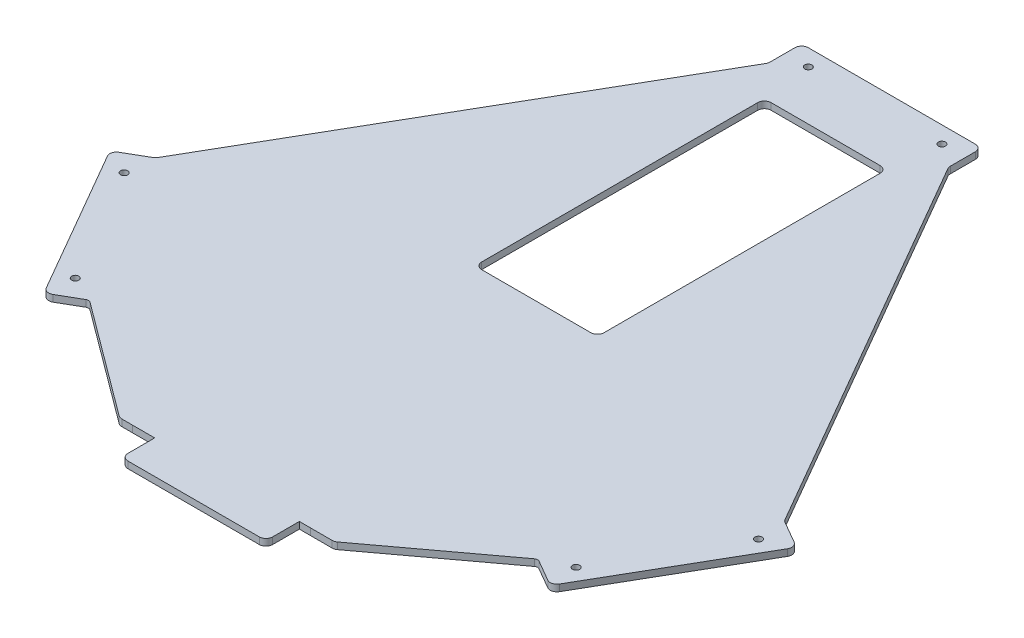
SolidWorks part; units mm, degrees
ref_plane "正面" through (0, 0, 0) normal (0, 0, 1) x (1, 0, 0)
ref_plane "平面" through (0, 0, 0) normal (0, 1, 0) x (1, 0, 0)
ref_plane "右側面" through (0, 0, 0) normal (1, 0, 0) x (0, 0, -1)
sketch "ｽｹｯﾁ1" plane through (0, 0, 0) normal (0, 1, 0) x (1, 0, 0)
  line L0 (341.7223, -98.5666) -> (163.7541, 4.1834) construction
  line L1 (85.5, 139.7235) -> (163.7541, 4.1834) construction
  line L2 (85.5, 345.2235) -> (85.5, 139.7235) construction
  line L3 (-275.2349, -158.9069) -> (275.2349, -158.9069)
  line L4 (275.2349, -158.9069) -> (0, 317.8138)
  line L5 (0, 317.8138) -> (-275.2349, -158.9069)
  line L6 (-275.2349, -158.9069) -> (275.2349, -158.9069)
  line L7 (275.2349, -158.9069) -> (0, 317.8138)
  line L8 (0, 317.8138) -> (-275.2349, -158.9069)
  line L9 (0, 450) -> (-389.7114, -225)
  line L10 (-389.7114, -225) -> (389.7114, -225)
  line L11 (389.7114, -225) -> (0, 450)
  line L12 (0, 450) -> (-389.7114, -225)
  line L13 (-389.7114, -225) -> (389.7114, -225)
  line L14 (389.7114, -225) -> (0, 450)
  line L15 (-70.5, 139.7235) -> (70.5, 139.7235) construction
  line L16 (-85.7541, -130.9165) -> (-156.2541, -8.807) construction
  line L17 (156.2541, -8.807) -> (85.7541, -130.9165) construction
  line L18 (0, 0) -> (259.8076, -150) construction
  line L19 (0, 0) -> (-259.8076, -150) construction
  line L20 (0, 0) -> (0, 300) construction
  line L21 (-341.7223, -98.5666) -> (-163.7541, 4.1834) construction
  line L22 (-163.7541, 4.1834) -> (-85.5, 139.7235) construction
  line L23 (-85.5, 345.2235) -> (-85.5, 139.7235) construction
  line L24 (256.2223, -246.6569) -> (78.2541, -143.9069) construction
  line L25 (78.2541, -143.9069) -> (-78.2541, -143.9069) construction
  line L26 (-256.2223, -246.6569) -> (-78.2541, -143.9069) construction
  line L27 (341.7223, -98.5666) -> (163.7541, 4.1834)
  line L28 (85.5, 139.7235) -> (163.7541, 4.1834)
  line L29 (85.5, 345.2235) -> (85.5, 139.7235)
  line L30 (-70.5, 139.7235) -> (70.5, 139.7235)
  line L31 (-85.7541, -130.9165) -> (-156.2541, -8.807)
  line L32 (156.2541, -8.807) -> (85.7541, -130.9165)
  line L33 (0, 0) -> (259.8076, -150)
  line L34 (0, 0) -> (-259.8076, -150)
  line L35 (0, 0) -> (0, 300)
  line L36 (-341.7223, -98.5666) -> (-163.7541, 4.1834)
  line L37 (-163.7541, 4.1834) -> (-85.5, 139.7235)
  line L38 (-85.5, 345.2235) -> (-85.5, 139.7235)
  line L39 (256.2223, -246.6569) -> (78.2541, -143.9069)
  line L40 (78.2541, -143.9069) -> (-78.2541, -143.9069)
  line L41 (-256.2223, -246.6569) -> (-78.2541, -143.9069)
  line L42 (-40.5, 140.8727) -> (-40.5, 153.6419) construction
  line L43 (-41.4674, 155.2072) -> (-70.1305, 169.5387) construction
  line L44 (-70.9131, 169.7235) -> (-84.4896, 169.7235) construction
  line L45 (-86.0052, 168.8485) -> (-112.6154, 122.7583) construction
  line L46 (-111.9748, 120.3677) -> (-101.2625, 114.1829) construction
  line L47 (-99.6921, 114.0926) -> (-41.5546, 139.2668) construction
  line L48 (70.1305, 169.5387) -> (41.4674, 155.2072) construction
  line L49 (40.5, 153.6419) -> (40.5, 140.8727) construction
  line L50 (41.5546, 139.2668) -> (99.6921, 114.0926) construction
  line L51 (101.2625, 114.1829) -> (111.9748, 120.3677) construction
  line L52 (112.6154, 122.7583) -> (86.0052, 168.8485) construction
  line L53 (84.4896, 169.7235) -> (70.9131, 169.7235) construction
  line L54 (142.2494, -35.3623) -> (153.3078, -41.7469) construction
  line L55 (155.147, -41.6918) -> (181.8901, -24.0346) construction
  line L56 (182.4414, -23.4492) -> (189.2297, -11.6916) construction
  line L57 (189.2297, -9.9416) -> (162.6195, 36.1486) construction
  line L58 (160.2289, 36.7892) -> (149.5165, 30.6044) construction
  line L59 (148.6531, 29.2896) -> (141.3859, -33.6461) construction
  line L60 (111.7596, -145.5042) -> (113.6797, -113.5154) construction
  line L61 (112.8078, -111.895) -> (101.7494, -105.5104) construction
  line L62 (99.8313, -105.6208) -> (48.961, -143.3822) construction
  line L63 (48.2541, -144.7873) -> (48.2541, -157.1569) construction
  line L64 (50.0041, -158.9069) -> (103.2245, -158.9069) construction
  line L65 (104.74, -158.0319) -> (111.5283, -146.2743) construction
  line L66 (-101.7494, -105.5104) -> (-112.8078, -111.895) construction
  line L67 (-113.6797, -113.5154) -> (-111.7596, -145.5042) construction
  line L68 (-111.5283, -146.2743) -> (-104.74, -158.0319) construction
  line L69 (-103.2245, -158.9069) -> (-50.0041, -158.9069) construction
  line L70 (-48.2541, -157.1569) -> (-48.2541, -144.7873) construction
  line L71 (-48.961, -143.3822) -> (-99.8313, -105.6208) construction
  line L72 (-181.8901, -24.0346) -> (-155.147, -41.6918) construction
  line L73 (-153.3078, -41.7469) -> (-142.2494, -35.3623) construction
  line L74 (-141.3859, -33.6461) -> (-148.6531, 29.2896) construction
  line L75 (-149.5165, 30.6044) -> (-160.2289, 36.7892) construction
  line L76 (-162.6195, 36.1486) -> (-189.2297, -9.9416) construction
  line L77 (-189.2297, -11.6916) -> (-182.4414, -23.4492) construction
  line L78 (-40.5, 140.8727) -> (-40.5, 153.6419)
  line L79 (-41.4674, 155.2072) -> (-70.1305, 169.5387)
  line L80 (-70.9131, 169.7235) -> (-84.4896, 169.7235)
  line L81 (-86.0052, 168.8485) -> (-112.6154, 122.7583)
  line L82 (-111.9748, 120.3677) -> (-101.2625, 114.1829)
  line L83 (-99.6921, 114.0926) -> (-41.5546, 139.2668)
  line L84 (70.1305, 169.5387) -> (41.4674, 155.2072)
  line L85 (40.5, 153.6419) -> (40.5, 140.8727)
  line L86 (41.5546, 139.2668) -> (99.6921, 114.0926)
  line L87 (101.2625, 114.1829) -> (111.9748, 120.3677)
  line L88 (112.6154, 122.7583) -> (86.0052, 168.8485)
  line L89 (84.4896, 169.7235) -> (70.9131, 169.7235)
  line L90 (142.2494, -35.3623) -> (153.3078, -41.7469)
  line L91 (155.147, -41.6918) -> (181.8901, -24.0346)
  line L92 (182.4414, -23.4492) -> (189.2297, -11.6916)
  line L93 (189.2297, -9.9416) -> (162.6195, 36.1486)
  line L94 (160.2289, 36.7892) -> (149.5165, 30.6044)
  line L95 (148.6531, 29.2896) -> (141.3859, -33.6461)
  line L96 (111.7596, -145.5042) -> (113.6797, -113.5154)
  line L97 (112.8078, -111.895) -> (101.7494, -105.5104)
  line L98 (99.8313, -105.6208) -> (48.961, -143.3822)
  line L99 (48.2541, -144.7873) -> (48.2541, -157.1569)
  line L100 (50.0041, -158.9069) -> (103.2245, -158.9069)
  line L101 (104.74, -158.0319) -> (111.5283, -146.2743)
  line L102 (-101.7494, -105.5104) -> (-112.8078, -111.895)
  line L103 (-113.6797, -113.5154) -> (-111.7596, -145.5042)
  line L104 (-111.5283, -146.2743) -> (-104.74, -158.0319)
  line L105 (-103.2245, -158.9069) -> (-50.0041, -158.9069)
  line L106 (-48.2541, -157.1569) -> (-48.2541, -144.7873)
  line L107 (-48.961, -143.3822) -> (-99.8313, -105.6208)
  line L108 (-181.8901, -24.0346) -> (-155.147, -41.6918)
  line L109 (-153.3078, -41.7469) -> (-142.2494, -35.3623)
  line L110 (-141.3859, -33.6461) -> (-148.6531, 29.2896)
  line L111 (-149.5165, 30.6044) -> (-160.2289, 36.7892)
  line L112 (-162.6195, 36.1486) -> (-189.2297, -9.9416)
  line L113 (-189.2297, -11.6916) -> (-182.4414, -23.4492)
  arc A0 (-40.5, 153.6419) -> (-41.4674, 155.2072) centre (-42.25, 153.6419) ccw construction
  circle A1 centre (0, 0) radius 300
  circle A2 centre (0, 0) radius 300
  arc A3 (-70.1305, 169.5387) -> (-70.9131, 169.7235) centre (-70.9131, 167.9735) ccw construction
  arc A4 (-84.4896, 169.7235) -> (-86.0052, 168.8485) centre (-84.4896, 167.9735) ccw construction
  arc A5 (-112.6154, 122.7583) -> (-111.9748, 120.3677) centre (-111.0998, 121.8833) ccw construction
  arc A6 (-101.2625, 114.1829) -> (-99.6921, 114.0926) centre (-100.3875, 115.6985) ccw construction
  arc A7 (-41.5546, 139.2668) -> (-40.5, 140.8727) centre (-42.25, 140.8727) ccw construction
  arc A8 (41.4674, 155.2072) -> (40.5, 153.6419) centre (42.25, 153.6419) ccw construction
  arc A9 (40.5, 140.8727) -> (41.5546, 139.2668) centre (42.25, 140.8727) ccw construction
  arc A10 (99.6921, 114.0926) -> (101.2625, 114.1829) centre (100.3875, 115.6985) ccw construction
  arc A11 (111.9748, 120.3677) -> (112.6154, 122.7583) centre (111.0998, 121.8833) ccw construction
  arc A12 (86.0052, 168.8485) -> (84.4896, 169.7235) centre (84.4896, 167.9735) ccw construction
  arc A13 (70.9131, 169.7235) -> (70.1305, 169.5387) centre (70.9131, 167.9735) ccw construction
  arc A14 (153.3078, -41.7469) -> (155.147, -41.6918) centre (154.1828, -40.2314) ccw construction
  arc A15 (181.8901, -24.0346) -> (182.4414, -23.4492) centre (180.9259, -22.5742) ccw construction
  arc A16 (189.2297, -11.6916) -> (189.2297, -9.9416) centre (187.7141, -10.8166) ccw construction
  arc A17 (162.6195, 36.1486) -> (160.2289, 36.7892) centre (161.1039, 35.2736) ccw construction
  arc A18 (149.5165, 30.6044) -> (148.6531, 29.2896) centre (150.3915, 29.0889) ccw construction
  arc A19 (141.3859, -33.6461) -> (142.2494, -35.3623) centre (143.1244, -33.8468) ccw construction
  arc A20 (113.6797, -113.5154) -> (112.8078, -111.895) centre (111.9328, -113.4105) ccw construction
  arc A21 (101.7494, -105.5104) -> (99.8313, -105.6208) centre (100.8744, -107.0259) ccw construction
  arc A22 (48.961, -143.3822) -> (48.2541, -144.7873) centre (50.0041, -144.7873) ccw construction
  arc A23 (48.2541, -157.1569) -> (50.0041, -158.9069) centre (50.0041, -157.1569) ccw construction
  arc A24 (103.2245, -158.9069) -> (104.74, -158.0319) centre (103.2245, -157.1569) ccw construction
  arc A25 (111.5283, -146.2743) -> (111.7596, -145.5042) centre (110.0127, -145.3993) ccw construction
  arc A26 (-112.8078, -111.895) -> (-113.6797, -113.5154) centre (-111.9328, -113.4105) ccw construction
  arc A27 (-111.7596, -145.5042) -> (-111.5283, -146.2743) centre (-110.0127, -145.3993) ccw construction
  arc A28 (-104.74, -158.0319) -> (-103.2245, -158.9069) centre (-103.2245, -157.1569) ccw construction
  arc A29 (-50.0041, -158.9069) -> (-48.2541, -157.1569) centre (-50.0041, -157.1569) ccw construction
  arc A30 (-48.2541, -144.7873) -> (-48.961, -143.3822) centre (-50.0041, -144.7873) ccw construction
  arc A31 (-99.8313, -105.6208) -> (-101.7494, -105.5104) centre (-100.8744, -107.0259) ccw construction
  arc A32 (-155.147, -41.6918) -> (-153.3078, -41.7469) centre (-154.1828, -40.2314) ccw construction
  arc A33 (-142.2494, -35.3623) -> (-141.3859, -33.6461) centre (-143.1244, -33.8468) ccw construction
  arc A34 (-148.6531, 29.2896) -> (-149.5165, 30.6044) centre (-150.3915, 29.0889) ccw construction
  arc A35 (-160.2289, 36.7892) -> (-162.6195, 36.1486) centre (-161.1039, 35.2736) ccw construction
  arc A36 (-189.2297, -9.9416) -> (-189.2297, -11.6916) centre (-187.7141, -10.8166) ccw construction
  arc A37 (-182.4414, -23.4492) -> (-181.8901, -24.0346) centre (-180.9259, -22.5742) ccw construction
  arc A38 (-40.5, 153.6419) -> (-41.4674, 155.2072) centre (-42.25, 153.6419) ccw
  arc A39 (-70.1305, 169.5387) -> (-70.9131, 169.7235) centre (-70.9131, 167.9735) ccw
  arc A40 (-84.4896, 169.7235) -> (-86.0052, 168.8485) centre (-84.4896, 167.9735) ccw
  arc A41 (-112.6154, 122.7583) -> (-111.9748, 120.3677) centre (-111.0998, 121.8833) ccw
  arc A42 (-101.2625, 114.1829) -> (-99.6921, 114.0926) centre (-100.3875, 115.6985) ccw
  arc A43 (-41.5546, 139.2668) -> (-40.5, 140.8727) centre (-42.25, 140.8727) ccw
  arc A44 (41.4674, 155.2072) -> (40.5, 153.6419) centre (42.25, 153.6419) ccw
  arc A45 (40.5, 140.8727) -> (41.5546, 139.2668) centre (42.25, 140.8727) ccw
  arc A46 (99.6921, 114.0926) -> (101.2625, 114.1829) centre (100.3875, 115.6985) ccw
  arc A47 (111.9748, 120.3677) -> (112.6154, 122.7583) centre (111.0998, 121.8833) ccw
  arc A48 (86.0052, 168.8485) -> (84.4896, 169.7235) centre (84.4896, 167.9735) ccw
  arc A49 (70.9131, 169.7235) -> (70.1305, 169.5387) centre (70.9131, 167.9735) ccw
  arc A50 (153.3078, -41.7469) -> (155.147, -41.6918) centre (154.1828, -40.2314) ccw
  arc A51 (181.8901, -24.0346) -> (182.4414, -23.4492) centre (180.9259, -22.5742) ccw
  arc A52 (189.2297, -11.6916) -> (189.2297, -9.9416) centre (187.7141, -10.8166) ccw
  arc A53 (162.6195, 36.1486) -> (160.2289, 36.7892) centre (161.1039, 35.2736) ccw
  arc A54 (149.5165, 30.6044) -> (148.6531, 29.2896) centre (150.3915, 29.0889) ccw
  arc A55 (141.3859, -33.6461) -> (142.2494, -35.3623) centre (143.1244, -33.8468) ccw
  arc A56 (113.6797, -113.5154) -> (112.8078, -111.895) centre (111.9328, -113.4105) ccw
  arc A57 (101.7494, -105.5104) -> (99.8313, -105.6208) centre (100.8744, -107.0259) ccw
  arc A58 (48.961, -143.3822) -> (48.2541, -144.7873) centre (50.0041, -144.7873) ccw
  arc A59 (48.2541, -157.1569) -> (50.0041, -158.9069) centre (50.0041, -157.1569) ccw
  arc A60 (103.2245, -158.9069) -> (104.74, -158.0319) centre (103.2245, -157.1569) ccw
  arc A61 (111.5283, -146.2743) -> (111.7596, -145.5042) centre (110.0127, -145.3993) ccw
  arc A62 (-112.8078, -111.895) -> (-113.6797, -113.5154) centre (-111.9328, -113.4105) ccw
  arc A63 (-111.7596, -145.5042) -> (-111.5283, -146.2743) centre (-110.0127, -145.3993) ccw
  arc A64 (-104.74, -158.0319) -> (-103.2245, -158.9069) centre (-103.2245, -157.1569) ccw
  arc A65 (-50.0041, -158.9069) -> (-48.2541, -157.1569) centre (-50.0041, -157.1569) ccw
  arc A66 (-48.2541, -144.7873) -> (-48.961, -143.3822) centre (-50.0041, -144.7873) ccw
  arc A67 (-99.8313, -105.6208) -> (-101.7494, -105.5104) centre (-100.8744, -107.0259) ccw
  arc A68 (-155.147, -41.6918) -> (-153.3078, -41.7469) centre (-154.1828, -40.2314) ccw
  arc A69 (-142.2494, -35.3623) -> (-141.3859, -33.6461) centre (-143.1244, -33.8468) ccw
  arc A70 (-148.6531, 29.2896) -> (-149.5165, 30.6044) centre (-150.3915, 29.0889) ccw
  arc A71 (-160.2289, 36.7892) -> (-162.6195, 36.1486) centre (-161.1039, 35.2736) ccw
  arc A72 (-189.2297, -9.9416) -> (-189.2297, -11.6916) centre (-187.7141, -10.8166) ccw
  arc A73 (-182.4414, -23.4492) -> (-181.8901, -24.0346) centre (-180.9259, -22.5742) ccw
  dimension "D1" = 0
  dimension "D2" = 0
  dimension "D3" = 0
sketch "ｽｹｯﾁ3" plane through (0, 0, 0) normal (0, 1, 0) x (1, 0, 0)
  line L0 (-70.5, 139.7235) -> (70.5, 139.7235) construction
  line L1 (-40.5, 139.7235) -> (40.5, 139.7235)
  line L2 (-40.5, 139.7235) -> (-40.5, 154.7235)
  line L3 (-40.5, 154.7235) -> (40.5, 154.7235)
  line L4 (40.5, 139.7235) -> (40.5, 154.7235)
  line L5 (-40.5, 140.8727) -> (-40.5, 153.6419) construction
  line L6 (40.5, 153.6419) -> (40.5, 140.8727) construction
  line L7 (154.2445, -42.2877) -> (113.7445, -112.4358)
  line L8 (141.2541, -34.7877) -> (154.2445, -42.2877)
  line L9 (141.2541, -34.7877) -> (100.7541, -104.9358)
  line L10 (100.7541, -104.9358) -> (113.7445, -112.4358)
  line L11 (-113.7445, -112.4358) -> (-154.2445, -42.2877)
  line L12 (-100.7541, -104.9358) -> (-113.7445, -112.4358)
  line L13 (-100.7541, -104.9358) -> (-141.2541, -34.7877)
  line L14 (-141.2541, -34.7877) -> (-154.2445, -42.2877)
  line L15 (-40.5, 139.7235) -> (-141.2541, -34.7877)
  line L16 (-100.7541, -104.9358) -> (100.7541, -104.9358)
  line L17 (40.5, 139.7235) -> (141.2541, -34.7877)
  point P20 (0, 0)
  dimension "D1" = 15
  dimension "D2" = 3
extrude "ﾎﾞｽ - 押し出し1" add sketch "ｽｹｯﾁ3" along normal mid plane 3 contours L17 L1 L15 L13 L16 L9 | L13 L14 L11 L12 | L9 L10 L7 L8 | L1 L4 L3 L2 region at (0, 0, -147.2235) region at (0, 0, 0) region at (-127.4993, 0, 73.6117) region at (127.4993, 0, 73.6117)
fillet "ﾌｨﾚｯﾄ1" radius 3 12 edges at (141.2541, 0, 34.7877) (154.2445, 0, 42.2877) (113.7445, 0, 112.4358) (100.7541, 0, 104.9358) (-100.7541, 0, 104.9358) (-154.2445, 0, 42.2877) (-141.2541, 0, 34.7877) (-40.5, 0, -139.7235) (-40.5, 0, -154.7235) (40.5, 0, -154.7235) (40.5, 0, -139.7235) (-113.7445, 0, 112.4358)
sketch "ｽｹｯﾁ4" plane through (0, 1.5, 0) normal (0, 1, 0) x (1, 0, 0)
  line L0 (-40.5, 147.2235) -> (40.5, 147.2235) construction
  line L1 (0, 154.7235) -> (0, 147.2235) construction
  line L12 (115.2445, -109.8377) -> (152.7445, -44.8858)
  line L13 (151.6464, -40.7877) -> (141.9502, -35.1896)
  line L14 (140.8522, -34.0916) -> (40.9019, 139.0273)
  line L15 (40.5, 140.5273) -> (40.5, 151.7235)
  line L16 (37.5, 154.7235) -> (-37.5, 154.7235)
  line L17 (-40.5, 151.7235) -> (-40.5, 140.5273)
  line L18 (-40.9019, 139.0273) -> (-140.8522, -34.0916)
  line L19 (-141.9502, -35.1896) -> (-151.6464, -40.7877)
  line L20 (-152.7445, -44.8858) -> (-115.2445, -109.8377)
  line L21 (-111.1464, -110.9358) -> (-101.4502, -105.3377)
  line L22 (-99.9502, -104.9358) -> (99.9502, -104.9358)
  line L23 (101.4502, -105.3377) -> (111.1464, -110.9358)
  line L24 (115.2445, -109.8377) -> (152.7445, -44.8858)
  line L25 (151.6464, -40.7877) -> (141.9502, -35.1896)
  line L26 (140.8522, -34.0916) -> (40.9019, 139.0273)
  line L27 (40.5, 140.5273) -> (40.5, 151.7235)
  line L28 (37.5, 154.7235) -> (-37.5, 154.7235)
  line L29 (-40.5, 151.7235) -> (-40.5, 140.5273)
  line L30 (-40.9019, 139.0273) -> (-140.8522, -34.0916)
  line L31 (-141.9502, -35.1896) -> (-151.6464, -40.7877)
  line L32 (-152.7445, -44.8858) -> (-115.2445, -109.8377)
  line L33 (-111.1464, -110.9358) -> (-101.4502, -105.3377)
  line L34 (-99.9502, -104.9358) -> (99.9502, -104.9358)
  line L35 (101.4502, -105.3377) -> (111.1464, -110.9358)
  circle A0 centre (-30, 147.2235) radius 1.6
  circle A1 centre (30, 147.2235) radius 1.6
  arc A12 (152.7445, -44.8858) -> (151.6464, -40.7877) centre (150.1464, -43.3858) ccw
  arc A13 (140.8522, -34.0916) -> (141.9502, -35.1896) centre (143.4502, -32.5916) ccw
  arc A14 (40.5, 140.5273) -> (40.9019, 139.0273) centre (43.5, 140.5273) ccw
  arc A15 (40.5, 151.7235) -> (37.5, 154.7235) centre (37.5, 151.7235) ccw
  arc A16 (-37.5, 154.7235) -> (-40.5, 151.7235) centre (-37.5, 151.7235) ccw
  arc A17 (-40.9019, 139.0273) -> (-40.5, 140.5273) centre (-43.5, 140.5273) ccw
  arc A18 (-141.9502, -35.1896) -> (-140.8522, -34.0916) centre (-143.4502, -32.5916) ccw
  arc A19 (-151.6464, -40.7877) -> (-152.7445, -44.8858) centre (-150.1464, -43.3858) ccw
  arc A20 (-115.2445, -109.8377) -> (-111.1464, -110.9358) centre (-112.6464, -108.3377) ccw
  arc A21 (-99.9502, -104.9358) -> (-101.4502, -105.3377) centre (-99.9502, -107.9358) ccw
  arc A22 (101.4502, -105.3377) -> (99.9502, -104.9358) centre (99.9502, -107.9358) ccw
  arc A23 (111.1464, -110.9358) -> (115.2445, -109.8377) centre (112.6464, -108.3377) ccw
  arc A24 (152.7445, -44.8858) -> (151.6464, -40.7877) centre (150.1464, -43.3858) ccw
  arc A25 (140.8522, -34.0916) -> (141.9502, -35.1896) centre (143.4502, -32.5916) ccw
  arc A26 (40.5, 140.5273) -> (40.9019, 139.0273) centre (43.5, 140.5273) ccw
  arc A27 (40.5, 151.7235) -> (37.5, 154.7235) centre (37.5, 151.7235) ccw
  arc A28 (-37.5, 154.7235) -> (-40.5, 151.7235) centre (-37.5, 151.7235) ccw
  arc A29 (-40.9019, 139.0273) -> (-40.5, 140.5273) centre (-43.5, 140.5273) ccw
  arc A30 (-141.9502, -35.1896) -> (-140.8522, -34.0916) centre (-143.4502, -32.5916) ccw
  arc A31 (-151.6464, -40.7877) -> (-152.7445, -44.8858) centre (-150.1464, -43.3858) ccw
  arc A32 (-115.2445, -109.8377) -> (-111.1464, -110.9358) centre (-112.6464, -108.3377) ccw
  arc A33 (-99.9502, -104.9358) -> (-101.4502, -105.3377) centre (-99.9502, -107.9358) ccw
  arc A34 (101.4502, -105.3377) -> (99.9502, -104.9358) centre (99.9502, -107.9358) ccw
  arc A35 (111.1464, -110.9358) -> (115.2445, -109.8377) centre (112.6464, -108.3377) ccw
  dimension "D3" = 3.2
  dimension "D2" = 7.5
  dimension "D4" = 30
  dimension "D1" = 0
extrude "ｶｯﾄ - 押し出し1" cut sketch "ｽｹｯﾁ4" against normal blind 3 contours A0 | A1 region at (-30, 1.5, -147.2235) region at (30, 1.5, -147.2235)
ref_axis "軸1" through (0, -1.65, 0) along (0, 1, 0)
pattern_circular "円形ﾊﾟﾀｰﾝ1" count 3 over 360 about axis through (0, -1.65, 0) along (0, 1, 0) of "ｶｯﾄ - 押し出し1"
sketch "ｽｹｯﾁ5" plane through (0, 1.5, 0) normal (0, 1, 0) x (1, 0, 0)
  line L0 (111.7596, -145.5042) -> (113.6797, -113.5154) construction
  line L1 (112.8078, -111.895) -> (101.7494, -105.5104) construction
  line L2 (99.8313, -105.6208) -> (48.961, -143.3822) construction
  line L3 (48.2541, -144.7873) -> (48.2541, -157.1569) construction
  line L4 (50.0041, -158.9069) -> (103.2245, -158.9069) construction
  line L5 (104.74, -158.0319) -> (111.5283, -146.2743) construction
  line L6 (78.255, -158.9069) -> (78.255, -143.9069) construction
  line L7 (78.255, -143.9069) -> (-78.255, -143.9069) construction
  line L8 (-78.255, -143.9069) -> (-78.255, -158.9069) construction
  line L9 (-78.255, -158.9069) -> (78.255, -158.9069) construction
  line L10 (-101.7494, -105.5104) -> (-112.8078, -111.895) construction
  line L11 (-113.6797, -113.5154) -> (-111.7596, -145.5042) construction
  line L12 (-111.5283, -146.2743) -> (-104.74, -158.0319) construction
  line L13 (-103.2245, -158.9069) -> (-50.0041, -158.9069) construction
  line L14 (-48.2541, -157.1569) -> (-48.2541, -144.7873) construction
  line L15 (-48.961, -143.3822) -> (-99.8313, -105.6208) construction
  line L16 (111.7596, -145.5042) -> (113.6797, -113.5154)
  line L17 (112.8078, -111.895) -> (101.7494, -105.5104)
  line L18 (99.8313, -105.6208) -> (48.961, -143.3822)
  line L19 (48.2541, -144.7873) -> (48.2541, -157.1569)
  line L20 (50.0041, -158.9069) -> (103.2245, -158.9069)
  line L21 (104.74, -158.0319) -> (111.5283, -146.2743)
  line L22 (78.255, -158.9069) -> (78.255, -143.9069)
  line L23 (78.255, -143.9069) -> (-78.255, -143.9069)
  line L24 (-78.255, -143.9069) -> (-78.255, -158.9069)
  line L25 (-78.255, -158.9069) -> (78.255, -158.9069)
  line L26 (-101.7494, -105.5104) -> (-112.8078, -111.895)
  line L27 (-113.6797, -113.5154) -> (-111.7596, -145.5042)
  line L28 (-111.5283, -146.2743) -> (-104.74, -158.0319)
  line L29 (-103.2245, -158.9069) -> (-50.0041, -158.9069)
  line L30 (-48.2541, -157.1569) -> (-48.2541, -144.7873)
  line L31 (-48.961, -143.3822) -> (-99.8313, -105.6208)
  line L32 (32.5005, -143.9066) -> (32.4899, -302.4966) construction
  line L33 (32.4899, -302.4966) -> (42.4899, -302.4972) construction
  line L34 (42.4899, -302.4972) -> (42.5005, -143.9072) construction
  line L35 (42.5005, -143.9072) -> (32.5005, -143.9066) construction
  line L36 (-42.4995, -143.9066) -> (-42.5101, -302.4966) construction
  line L37 (-42.5101, -302.4966) -> (-32.5101, -302.4972) construction
  line L38 (-32.5101, -302.4972) -> (-32.4995, -143.9072) construction
  line L39 (-32.4995, -143.9072) -> (-42.4995, -143.9066) construction
  line L40 (32.5005, -143.9066) -> (32.4899, -302.4966)
  line L41 (32.4899, -302.4966) -> (42.4899, -302.4972)
  line L42 (42.4899, -302.4972) -> (42.5005, -143.9072)
  line L43 (42.5005, -143.9072) -> (32.5005, -143.9066)
  line L44 (115.2445, -109.8377) -> (152.7445, -44.8858)
  line L45 (151.6464, -40.7877) -> (141.9502, -35.1896)
  line L46 (140.8522, -34.0916) -> (40.9019, 139.0273)
  line L47 (40.5, 140.5273) -> (40.5, 151.7235)
  line L48 (37.5, 154.7235) -> (-37.5, 154.7235)
  line L49 (-40.5, 151.7235) -> (-40.5, 140.5273)
  line L50 (-40.9019, 139.0273) -> (-140.8522, -34.0916)
  line L51 (-141.9502, -35.1896) -> (-151.6464, -40.7877)
  line L52 (-152.7445, -44.8858) -> (-115.2445, -109.8377)
  line L53 (-111.1464, -110.9358) -> (-101.4502, -105.3377)
  line L54 (-99.9502, -104.9358) -> (99.9502, -104.9358)
  line L55 (101.4502, -105.3377) -> (111.1464, -110.9358)
  line L56 (115.2445, -109.8377) -> (152.7445, -44.8858)
  line L57 (151.6464, -40.7877) -> (141.9502, -35.1896)
  line L58 (140.8522, -34.0916) -> (40.9019, 139.0273)
  line L59 (40.5, 140.5273) -> (40.5, 151.7235)
  line L60 (37.5, 154.7235) -> (-37.5, 154.7235)
  line L61 (-40.5, 151.7235) -> (-40.5, 140.5273)
  line L62 (-40.9019, 139.0273) -> (-140.8522, -34.0916)
  line L63 (-141.9502, -35.1896) -> (-151.6464, -40.7877)
  line L64 (-152.7445, -44.8858) -> (-115.2445, -109.8377)
  line L65 (-111.1464, -110.9358) -> (-101.4502, -105.3377)
  line L66 (-99.9502, -104.9358) -> (99.9502, -104.9358)
  line L67 (101.4502, -105.3377) -> (111.1464, -110.9358)
  line L68 (-42.4995, -143.9066) -> (-42.5101, -302.4966)
  line L69 (-42.5101, -302.4966) -> (-32.5101, -302.4972)
  line L70 (-32.5101, -302.4972) -> (-32.4995, -143.9072)
  line L71 (-32.4995, -143.9072) -> (-42.4995, -143.9066)
  arc A0 (113.6797, -113.5154) -> (112.8078, -111.895) centre (111.9328, -113.4105) ccw construction
  arc A1 (101.7494, -105.5104) -> (99.8313, -105.6208) centre (100.8744, -107.0259) ccw construction
  arc A2 (48.961, -143.3822) -> (48.2541, -144.7873) centre (50.0041, -144.7873) ccw construction
  arc A3 (48.2541, -157.1569) -> (50.0041, -158.9069) centre (50.0041, -157.1569) ccw construction
  arc A4 (103.2245, -158.9069) -> (104.74, -158.0319) centre (103.2245, -157.1569) ccw construction
  arc A5 (111.5283, -146.2743) -> (111.7596, -145.5042) centre (110.0127, -145.3993) ccw construction
  arc A6 (-112.8078, -111.895) -> (-113.6797, -113.5154) centre (-111.9328, -113.4105) ccw construction
  arc A7 (-111.7596, -145.5042) -> (-111.5283, -146.2743) centre (-110.0127, -145.3993) ccw construction
  arc A8 (-104.74, -158.0319) -> (-103.2245, -158.9069) centre (-103.2245, -157.1569) ccw construction
  arc A9 (-50.0041, -158.9069) -> (-48.2541, -157.1569) centre (-50.0041, -157.1569) ccw construction
  arc A10 (-48.2541, -144.7873) -> (-48.961, -143.3822) centre (-50.0041, -144.7873) ccw construction
  arc A11 (-99.8313, -105.6208) -> (-101.7494, -105.5104) centre (-100.8744, -107.0259) ccw construction
  arc A12 (113.6797, -113.5154) -> (112.8078, -111.895) centre (111.9328, -113.4105) ccw
  arc A13 (101.7494, -105.5104) -> (99.8313, -105.6208) centre (100.8744, -107.0259) ccw
  arc A14 (48.961, -143.3822) -> (48.2541, -144.7873) centre (50.0041, -144.7873) ccw
  arc A15 (48.2541, -157.1569) -> (50.0041, -158.9069) centre (50.0041, -157.1569) ccw
  arc A16 (103.2245, -158.9069) -> (104.74, -158.0319) centre (103.2245, -157.1569) ccw
  arc A17 (111.5283, -146.2743) -> (111.7596, -145.5042) centre (110.0127, -145.3993) ccw
  arc A18 (-112.8078, -111.895) -> (-113.6797, -113.5154) centre (-111.9328, -113.4105) ccw
  arc A19 (-111.7596, -145.5042) -> (-111.5283, -146.2743) centre (-110.0127, -145.3993) ccw
  arc A20 (-104.74, -158.0319) -> (-103.2245, -158.9069) centre (-103.2245, -157.1569) ccw
  arc A21 (-50.0041, -158.9069) -> (-48.2541, -157.1569) centre (-50.0041, -157.1569) ccw
  arc A22 (-48.2541, -144.7873) -> (-48.961, -143.3822) centre (-50.0041, -144.7873) ccw
  arc A23 (-99.8313, -105.6208) -> (-101.7494, -105.5104) centre (-100.8744, -107.0259) ccw
  arc A36 (152.7445, -44.8858) -> (151.6464, -40.7877) centre (150.1464, -43.3858) ccw
  arc A37 (140.8522, -34.0916) -> (141.9502, -35.1896) centre (143.4502, -32.5916) ccw
  arc A38 (40.5, 140.5273) -> (40.9019, 139.0273) centre (43.5, 140.5273) ccw
  arc A39 (40.5, 151.7235) -> (37.5, 154.7235) centre (37.5, 151.7235) ccw
  arc A40 (-37.5, 154.7235) -> (-40.5, 151.7235) centre (-37.5, 151.7235) ccw
  arc A41 (-40.9019, 139.0273) -> (-40.5, 140.5273) centre (-43.5, 140.5273) ccw
  arc A42 (-141.9502, -35.1896) -> (-140.8522, -34.0916) centre (-143.4502, -32.5916) ccw
  arc A43 (-151.6464, -40.7877) -> (-152.7445, -44.8858) centre (-150.1464, -43.3858) ccw
  arc A44 (-115.2445, -109.8377) -> (-111.1464, -110.9358) centre (-112.6464, -108.3377) ccw
  arc A45 (-99.9502, -104.9358) -> (-101.4502, -105.3377) centre (-99.9502, -107.9358) ccw
  arc A46 (101.4502, -105.3377) -> (99.9502, -104.9358) centre (99.9502, -107.9358) ccw
  arc A47 (111.1464, -110.9358) -> (115.2445, -109.8377) centre (112.6464, -108.3377) ccw
  arc A48 (152.7445, -44.8858) -> (151.6464, -40.7877) centre (150.1464, -43.3858) ccw
  arc A49 (140.8522, -34.0916) -> (141.9502, -35.1896) centre (143.4502, -32.5916) ccw
  arc A50 (40.5, 140.5273) -> (40.9019, 139.0273) centre (43.5, 140.5273) ccw
  arc A51 (40.5, 151.7235) -> (37.5, 154.7235) centre (37.5, 151.7235) ccw
  arc A52 (-37.5, 154.7235) -> (-40.5, 151.7235) centre (-37.5, 151.7235) ccw
  arc A53 (-40.9019, 139.0273) -> (-40.5, 140.5273) centre (-43.5, 140.5273) ccw
  arc A54 (-141.9502, -35.1896) -> (-140.8522, -34.0916) centre (-143.4502, -32.5916) ccw
  arc A55 (-151.6464, -40.7877) -> (-152.7445, -44.8858) centre (-150.1464, -43.3858) ccw
  arc A56 (-115.2445, -109.8377) -> (-111.1464, -110.9358) centre (-112.6464, -108.3377) ccw
  arc A57 (-99.9502, -104.9358) -> (-101.4502, -105.3377) centre (-99.9502, -107.9358) ccw
  arc A58 (101.4502, -105.3377) -> (99.9502, -104.9358) centre (99.9502, -107.9358) ccw
  arc A59 (111.1464, -110.9358) -> (115.2445, -109.8377) centre (112.6464, -108.3377) ccw
  line M46 (-111.1464, -110.9358) -> (-101.4502, -105.3377)
  arc M47 (-101.4502, -105.3377) -> (-99.9502, -104.9358) centre (-99.9502, -107.9358) cw
  line M48 (-99.9502, -104.9358) -> (99.9502, -104.9358)
  arc M49 (99.9502, -104.9358) -> (101.4502, -105.3377) centre (99.9502, -107.9358) cw
  line M50 (101.4502, -105.3377) -> (111.1464, -110.9358)
  dimension "D1" = 0
extrude "ﾎﾞｽ - 押し出し2" add sketch "ｽｹｯﾁ5" against normal blind 3 separate body contours A23 L31 A22 L23 L68 L71 L40 L43 A14 L18 A13 M50 M49 M48 M47 M46 | L71 L70 L25 L40 L23 region at (0, 1.5, 122.1322) region at (0, 1.5, 151.4069)
fillet "ﾌｨﾚｯﾄ2" radius 3 4 edges at (48.4917, 0, 143.9069) (32.4995, 0, 158.9069) (-32.5005, 0, 158.9069) (-48.4917, 0, 143.9069)
sketch "ｽｹｯﾁ6" plane through (0, -1.5, 0) normal (0, -1, 0) x (1, 0, 0)
  line L0 (0, 0) -> (0, -60) construction
  line L2 (-27.5, -125) -> (27.5, -125)
  line L3 (-27.5, -125) -> (-27.5, 5)
  line L4 (-27.5, 5) -> (27.5, 5)
  line L5 (27.5, -125) -> (27.5, 5)
  line L6 (-27.5, -125) -> (27.5, 5) construction
  line L7 (-27.5, 5) -> (27.5, -125) construction
  dimension "D1" = 60
  dimension "D2" = 130
  dimension "D3" = 55
extrude "ｶｯﾄ - 押し出し2" cut sketch "ｽｹｯﾁ6" against normal blind 10
fillet "ﾌｨﾚｯﾄ3" radius 3 4 edges at (27.5, 0, -125) (-27.5, 0, -125) (-27.5, 0, 5) (27.5, 0, 5)
combine bodies "組み合わせ1" operation type add bodies to combine 104 105
